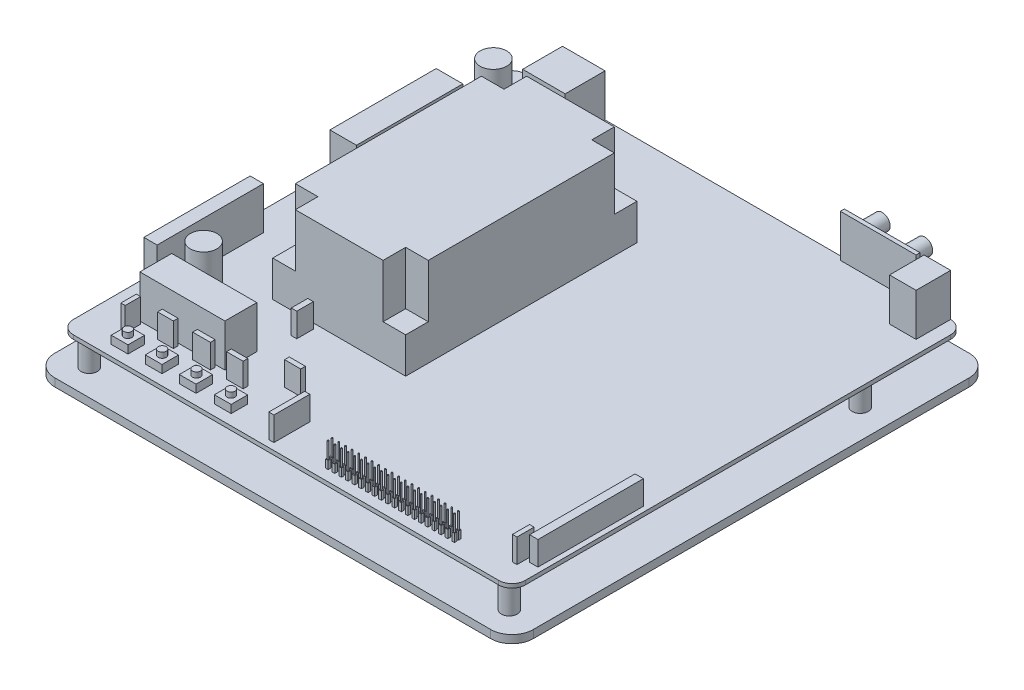
SolidWorks part; units mm, degrees
ref_plane "Plano frontal" through (0, 0, 0) normal (0, 0, 1) x (1, 0, 0)
ref_plane "Plano superior" through (0, 0, 0) normal (0, 1, 0) x (1, 0, 0)
ref_plane "Plano direito" through (0, 0, 0) normal (1, 0, 0) x (0, 0, -1)
sketch "Esboço1" plane through (0, 0, 0) normal (0, 1, 0) x (1, 0, 0)
  line L1 (82, -90) -> (-82, -90)
  line L2 (90, -82) -> (90, 82)
  line L3 (82, 90) -> (-82, 90)
  line L4 (-90, -82) -> (-90, 82)
  line L5 (90, -90) -> (-90, 90) construction
  line L6 (90, 90) -> (-90, -90) construction
  arc A0 (82, -90) -> (90, -82) centre (82, -82) ccw
  arc A1 (-82, -90) -> (-90, -82) centre (-82, -82) cw
  arc A2 (90, 82) -> (82, 90) centre (82, 82) ccw
  arc A3 (-82, 90) -> (-90, 82) centre (-82, 82) ccw
  point P0 (0, 0)
  dimension "D3" = 8
  dimension "D1" = 180
  dimension "D2" = 180
extrude "Ressalto-extrusão1" add sketch "Esboço1" along normal blind 3
sketch "Esboço2" plane through (0, 0, 0) normal (0, -1, 0) x (-1, 0, 0)
  line L0 (82, -90) -> (-82, -90) construction
  line L1 (90, 82) -> (90, -82) construction
  line L2 (0, 0) -> (-90, 0) construction
  line L3 (-90, -82) -> (-90, 82) construction
  line L4 (0, 0) -> (0, -90) construction
  circle A0 centre (79, -62) radius 3.5
  circle A1 centre (-79, -62) radius 3.5
  circle A2 centre (-79, 62) radius 3.5
  circle A3 centre (79, 62) radius 3.5
  dimension "D1" = 7
  dimension "D2" = 28
  dimension "D3" = 11
extrude "Ressalto-extrusão2" add sketch "Esboço2" along normal blind 5
sketch "Esboço3" plane through (0, 3, 0) normal (0, 1, 0) x (1, 0, 0)
  line L0 (90, -82) -> (90, 82) construction
  line L1 (-82, -90) -> (82, -90) construction
  line L2 (-90, 82) -> (-90, -82) construction
  line L3 (82, 90) -> (-82, 90) construction
  circle A0 centre (-79, -80) radius 3
  circle A1 centre (-79, 75) radius 3
  circle A2 centre (79, 52) radius 3
  circle A3 centre (79, -80) radius 3
  dimension "D1" = 6
  dimension "D3" = 11
  dimension "D5" = 10
  dimension "D6" = 38
  dimension "D2" = 10
  dimension "D4" = 11
  dimension "D7" = 15
extrude "Ressalto-extrusão3" add sketch "Esboço3" along normal blind 11
sketch "Esboço4" plane through (0, 14, 0) normal (0, 1, 0) x (1, 0, 0)
  line L1 (-80, 85) -> (80, 85)
  line L2 (-85, 80) -> (-85, -80)
  line L3 (-80, -85) -> (80, -85)
  line L4 (85, 80) -> (85, -80)
  line L5 (-85, 85) -> (85, -85) construction
  line L6 (-85, -85) -> (85, 85) construction
  arc A1 (80, -85) -> (85, -80) centre (80, -80) ccw
  arc A2 (-85, -80) -> (-80, -85) centre (-80, -80) ccw
  arc A3 (80, 85) -> (85, 80) centre (80, 80) cw
  arc A4 (-80, 85) -> (-85, 80) centre (-80, 80) ccw
  point P0 (0, 0)
  dimension "D3" = 5
  dimension "D1" = 170
  dimension "D2" = 170
extrude "Ressalto-extrusão4" add sketch "Esboço4" along normal blind 1.5
sketch "Esboço5" plane through (0, 15.5, 0) normal (0, 1, 0) x (1, 0, 0)
  line L0 (-80, -85) -> (80, -85) construction
  line L1 (-54, 51) -> (-4, 51)
  line L2 (-54, 51) -> (-54, -36)
  line L3 (-54, -36) -> (-4, -36)
  line L4 (-4, 51) -> (-4, -36)
  line L5 (-54, 51) -> (-4, -36) construction
  line L6 (-54, -36) -> (-4, 51) construction
  line L7 (-85, 80) -> (-85, -80) construction
  point P0 (-29, 7.5)
  dimension "D1" = 50
  dimension "D2" = 87
  dimension "D3" = 49
  dimension "D4" = 31
extrude "Ressalto-extrusão5" add sketch "Esboço5" along normal blind 33.5
sketch "Esboço6" plane through (0, 49, 0) normal (0, 1, 0) x (1, 0, 0)
  line L0 (-54, 7.5) -> (-4, 7.5) construction
  line L1 (-54, -36) -> (-45.5, -36)
  line L2 (-54, -36) -> (-54, -27.5)
  line L3 (-54, -27.5) -> (-45.5, -27.5)
  line L4 (-45.5, -36) -> (-45.5, -27.5)
  line L5 (-54, 51) -> (-54, -36) construction
  line L6 (-4, -36) -> (-4, 51) construction
  line L7 (-29, 51) -> (-29, -36) construction
  line L8 (-4, 51) -> (-54, 51) construction
  line L9 (-54, -36) -> (-4, -36) construction
  line L10 (-12.5, -36) -> (-12.5, -27.5)
  line L11 (-4, -36) -> (-12.5, -36)
  line L12 (-4, -36) -> (-4, -27.5)
  line L13 (-4, -27.5) -> (-12.5, -27.5)
  line L14 (-4, 42.5) -> (-12.5, 42.5)
  line L15 (-4, 51) -> (-4, 42.5)
  line L16 (-4, 51) -> (-12.5, 51)
  line L17 (-12.5, 51) -> (-12.5, 42.5)
  line L18 (-45.5, 51) -> (-45.5, 42.5)
  line L19 (-54, 42.5) -> (-45.5, 42.5)
  line L20 (-54, 51) -> (-54, 42.5)
  line L21 (-54, 51) -> (-45.5, 51)
  dimension "D1" = 8.5
  dimension "D2" = 8.5
extrude "Corte-extrusão1" cut sketch "Esboço6" against normal blind 20
sketch "Esboço7" plane through (0, 15.5, 0) normal (0, 1, 0) x (1, 0, 0)
  line L0 (-30.95, -74.8) -> (-24.65, -74.8)
  line L1 (-69.75, -74.8) -> (-63.45, -74.8)
  line L2 (-69.75, -74.8) -> (-69.75, -81)
  line L3 (-69.75, -81) -> (-63.45, -81)
  line L4 (-63.45, -74.8) -> (-63.45, -81)
  line L5 (-69.75, -74.8) -> (-63.45, -81) construction
  line L6 (-69.75, -81) -> (-63.45, -74.8) construction
  line L7 (-80, -85) -> (80, -85) construction
  line L8 (-85, 80) -> (-85, -80) construction
  line L9 (-56.95, -74.8) -> (-50.65, -74.8)
  line L10 (-56.95, -74.8) -> (-56.95, -81)
  line L11 (-56.95, -81) -> (-50.65, -81)
  line L12 (-50.65, -74.8) -> (-50.65, -81)
  line L13 (-56.95, -74.8) -> (-50.65, -81) construction
  line L14 (-56.95, -81) -> (-50.65, -74.8) construction
  line L15 (-44.15, -74.8) -> (-37.85, -74.8)
  line L16 (-44.15, -74.8) -> (-44.15, -81)
  line L17 (-44.15, -81) -> (-37.85, -81)
  line L18 (-37.85, -74.8) -> (-37.85, -81)
  line L19 (-44.15, -74.8) -> (-37.85, -81) construction
  line L20 (-44.15, -81) -> (-37.85, -74.8) construction
  line L21 (-30.95, -74.8) -> (-30.95, -81)
  line L22 (-30.95, -81) -> (-24.65, -81)
  line L23 (-24.65, -74.8) -> (-24.65, -81)
  line L24 (-30.95, -74.8) -> (-24.65, -81) construction
  line L25 (-30.95, -81) -> (-24.65, -74.8) construction
  point P0 (-66.6, -77.9)
  point P10 (-27.8, -77.9)
  point P11 (-53.8, -77.9)
  point P16 (-41, -77.9)
  dimension "D1" = 6.2
  dimension "D2" = 6.3
  dimension "D3" = 4
  dimension "D4" = 15.25
  dimension "D5" = 3
  dimension "D6" = 6.5
  dimension "D8" = 6.9
  dimension "D7" = 2
extrude "Ressalto-extrusão6" add sketch "Esboço7" along normal blind 3
sketch "Esboço8" plane through (0, 18.5, 0) normal (0, 1, 0) x (1, 0, 0)
  line L0 (-63.45, -81) -> (-63.45, -74.8) construction
  line L2 (-69.75, -81) -> (-63.45, -81) construction
  line L3 (-24.65, -81) -> (-24.65, -74.8) construction
  line L4 (-24.65, -74.8) -> (-30.95, -74.8) construction
  circle A0 centre (-66.6, -77.9) radius 1.5
  circle A1 centre (-53.7, -77.9) radius 1.5
  circle A2 centre (-40.8, -77.9) radius 1.5
  circle A3 centre (-27.75, -77.95) radius 1.5
  point P6 (-66.6, -81)
  dimension "D1" = 3.15
  dimension "D2" = 3.1
  dimension "D3" = 3
  dimension "D5" = 3
  dimension "D6" = 3.1
  dimension "D7" = 3.15
  dimension "D8" = 12.9
  dimension "D4" = 3
extrude "Ressalto-extrusão7" add sketch "Esboço8" along normal blind 2
sketch "Esboço9" plane through (0, 15.5, 0) normal (0, 1, 0) x (1, 0, 0)
  line L0 (-80, -85) -> (80, -85) construction
  line L1 (10.85, -80) -> (11.85, -80)
  line L2 (10.85, -80) -> (10.85, -81)
  line L3 (10.85, -81) -> (11.85, -81)
  line L4 (11.85, -80) -> (11.85, -81)
  line L5 (10.85, -80) -> (11.85, -81) construction
  line L6 (10.85, -81) -> (11.85, -80) construction
  line L7 (-24.65, -81) -> (-24.65, -74.8) construction
  point P0 (11.35, -80.5)
  dimension "D1" = 1
  dimension "D2" = 4
  dimension "D3" = 35.5
extrude "Ressalto-extrusão8" add sketch "Esboço9" along normal blind 3
sketch "Esboço10" plane through (0, 18.5, 0) normal (0, 1, 0) x (1, 0, 0)
  line L1 (11.35, -80) -> (11.35, -80.5) construction
  line L2 (11.85, -80) -> (10.85, -80) construction
  line L3 (11.35, -80.5) -> (11.85, -80.5) construction
  line L4 (11.85, -81) -> (11.85, -80) construction
  circle A0 centre (11.35, -80.5) radius 0.25
  dimension "D1" = 0.5
extrude "Ressalto-extrusão9" add sketch "Esboço10" along normal blind 6
pattern_linear "Padrão linear1" count 20 spacing 2.5 along (1, 0, 0) count 2 spacing 1.5 along (0, 0, -1) of "Ressalto-extrusão8", "Ressalto-extrusão9"
sketch "Esboço11" plane through (0, 15.5, 0) normal (0, 1, 0) x (1, 0, 0)
  line L0 (80, 85) -> (-80, 85) construction
  line L1 (-71.9966, -56) -> (-39.9966, -56)
  line L2 (-71.9966, -56) -> (-71.9966, -68)
  line L3 (-71.9966, -68) -> (-39.9966, -68)
  line L4 (-39.9966, -56) -> (-39.9966, -68)
  line L5 (-82.5, -56) -> (-77.5, -56)
  line L6 (-82.5, -56) -> (-82.5, -16)
  line L7 (-82.5, -16) -> (-77.5, -16)
  line L8 (-77.5, -56) -> (-77.5, -16)
  line L9 (-82.5, 54) -> (-72.5, 54)
  line L10 (-82.5, 54) -> (-82.5, 14)
  line L11 (-82.5, 14) -> (-72.5, 14)
  line L12 (-72.5, 54) -> (-72.5, 14)
  line L13 (-66, 85) -> (-50, 85)
  line L14 (-66, 85) -> (-66, 70)
  line L15 (-66, 70) -> (-50, 70)
  line L16 (-50, 85) -> (-50, 70)
  line L17 (-85, 80) -> (-85, -80) construction
  line L18 (-80, -85) -> (80, -85) construction
  line L19 (80, 85) -> (70, 85)
  line L20 (80, 85) -> (80, 72)
  line L21 (80, 72) -> (70, 72)
  line L22 (70, 85) -> (70, 72)
  line L23 (68.5, 85) -> (40, 85)
  line L24 (68.5, 85) -> (68.5, 83.5)
  line L25 (68.5, 83.5) -> (40, 83.5)
  line L26 (40, 85) -> (40, 83.5)
  circle A0 centre (-70, -46) radius 5
  circle A1 centre (-75, 68) radius 5
  point P35 (0, 0)
  dimension "D1" = 10
  dimension "D2" = 10
  dimension "D12" = 17
  dimension "D26" = 10
  dimension "D3" = 15
  dimension "D4" = 16
  dimension "D5" = 19
  dimension "D6" = 13
  dimension "D7" = 10
  dimension "D8" = 28.5
  dimension "D9" = 1.5
  dimension "D10" = 1.5
  dimension "D11" = 10
  dimension "D13" = 10
  dimension "D14" = 40
  dimension "D15" = 2.5
  dimension "D16" = 2.5
  dimension "D17" = 5
  dimension "D18" = 29
  dimension "D19" = 30
  dimension "D20" = 40
  dimension "D21" = 7.5
  dimension "D22" = 12
  dimension "D23" = 32
  dimension "D24" = 13.0034
  dimension "D25" = 17
extrude "Ressalto-extrusão10" add sketch "Esboço11" along normal blind 16
sketch "Esboço12" plane through (0, 0, -85) normal (0, 0, -1) x (-1, 0, 0)
  line L0 (-68.5, 31.5) -> (-40, 31.5) construction
  line L1 (-62.25, 26.5) -> (-68.5, 26.5) construction
  line L2 (-68.5, 31.5) -> (-68.5, 15.5) construction
  line L3 (-46.25, 26.5) -> (-40, 26.5) construction
  line L4 (-40, 31.5) -> (-40, 15.5) construction
  circle A0 centre (-62.25, 26.5) radius 3
  circle A1 centre (-46.25, 26.5) radius 3
  dimension "D1" = 6
  dimension "D2" = 6
  dimension "D3" = 5
  dimension "D4" = 16
extrude "Ressalto-extrusão11" add sketch "Esboço12" along normal blind 8
sketch "Esboço13" plane through (0, 15.5, 0) normal (0, 1, 0) x (1, 0, 0)
  line L0 (-69.75, -74.8) -> (-69.75, -81) construction
  line L1 (-70.7943, -68.907) -> (-72.4259, -68.907)
  line L2 (-70.7943, -68.907) -> (-70.7943, -74.6918)
  line L3 (-70.7943, -74.6918) -> (-72.4259, -74.6918)
  line L4 (-72.4259, -68.907) -> (-72.4259, -74.6918)
  line L5 (-62.6363, -68.907) -> (-56.7033, -68.907)
  line L6 (-62.6363, -68.907) -> (-62.6363, -70.6869)
  line L7 (-62.6363, -70.6869) -> (-56.7033, -70.6869)
  line L8 (-56.7033, -68.907) -> (-56.7033, -70.6869)
  line L9 (-49.4353, -68.907) -> (-42.7606, -68.907)
  line L10 (-49.4353, -68.907) -> (-49.4353, -70.6869)
  line L11 (-49.4353, -70.6869) -> (-42.7606, -70.6869)
  line L12 (-42.7606, -68.907) -> (-42.7606, -70.6869)
  line L13 (-36.6792, -68.907) -> (-30.4495, -68.907)
  line L14 (-36.6792, -68.907) -> (-36.6792, -70.6869)
  line L15 (-36.6792, -70.6869) -> (-30.4495, -70.6869)
  line L16 (-30.4495, -68.907) -> (-30.4495, -70.6869)
  line L17 (-9.0905, -68.907) -> (-7.1623, -68.907)
  line L18 (-9.0905, -68.907) -> (-9.0905, -82.4047)
  line L19 (-9.0905, -82.4047) -> (-7.1623, -82.4047)
  line L20 (-7.1623, -68.907) -> (-7.1623, -82.4047)
  line L21 (-23.1815, -60.6008) -> (-17.1002, -60.6008)
  line L22 (-23.1815, -60.6008) -> (-23.1815, -62.3807)
  line L23 (-23.1815, -62.3807) -> (-17.1002, -62.3807)
  line L24 (-17.1002, -60.6008) -> (-17.1002, -62.3807)
  line L25 (-38.7558, -38.0552) -> (-36.6792, -38.0552)
  line L26 (-38.7558, -38.0552) -> (-38.7558, -44.2849)
  line L27 (-38.7558, -44.2849) -> (-36.6792, -44.2849)
  line L28 (-36.6792, -38.0552) -> (-36.6792, -44.2849)
  line L29 (83.0751, -73.3111) -> (79.9494, -73.3111)
  line L30 (83.0751, -73.3111) -> (83.0751, -33.6552)
  line L31 (83.0751, -33.6552) -> (79.9494, -33.6552)
  line L32 (79.9494, -73.3111) -> (79.9494, -33.6552)
  line L33 (78.3022, -70.0067) -> (76.6024, -70.0067)
  line L34 (78.3022, -70.0067) -> (78.3022, -76.444)
  line L35 (78.3022, -76.444) -> (76.6024, -76.444)
  line L36 (76.6024, -70.0067) -> (76.6024, -76.444)
  line L37 (-63.45, -74.8) -> (-69.75, -74.8) construction
  point P36 (76.8059, -71.7664)
  point P37 (76.6024, -70.7158)
  dimension "D1" = 7.1137
  dimension "D2" = 13.0467
  dimension "D3" = 20.3147
  dimension "D4" = 26.9894
  dimension "D5" = 30.9942
  dimension "D6" = 33.0708
  dimension "D7" = 39.3005
  dimension "D8" = 46.5685
  dimension "D9" = 52.6498
  dimension "D10" = 60.6595
  dimension "D11" = 62.5877
  dimension "D12" = 146.3524
  dimension "D13" = 148.0522
  dimension "D14" = 149.6994
  dimension "D15" = 152.8251
  dimension "D16" = 1.0443
  dimension "D17" = 2.6759
  dimension "D18" = 0.1082
  dimension "D19" = 1.4889
  dimension "D20" = 4.1131
  dimension "D21" = 4.7933
  dimension "D22" = 5.893
  dimension "D23" = 12.4193
  dimension "D24" = 30.5151
  dimension "D27" = 41.1448
  dimension "D28" = 1.644
  dimension "D29" = 7.6047
extrude "Ressalto-extrusão12" add sketch "Esboço13" along normal blind 9
